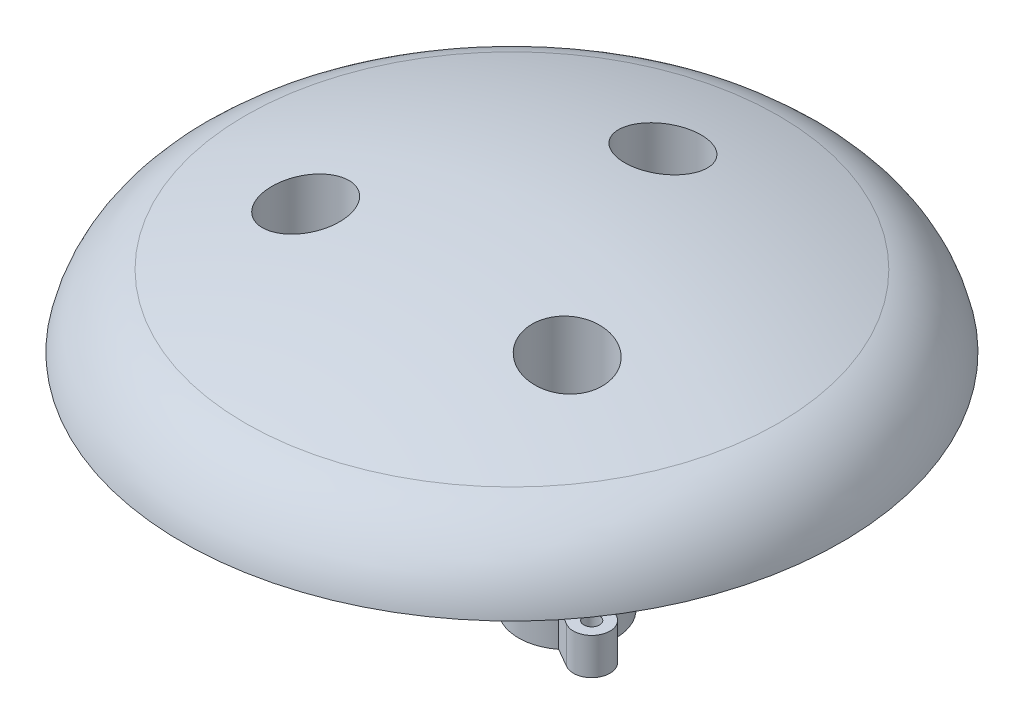
SolidWorks part; units mm, degrees
ref_plane "Alzado" through (0, 0, 0) normal (0, 0, 1) x (1, 0, 0)
ref_plane "Planta" through (0, 0, 0) normal (0, 1, 0) x (1, 0, 0)
ref_plane "Vista lateral" through (0, 0, 0) normal (1, 0, 0) x (0, 0, -1)
sketch "Croquis1" plane through (0, 0, 0) normal (0, 1, 0) x (1, 0, 0)
  line L1 (0, 28.8675) -> (-25, -14.4338) construction
  line L2 (-25, -14.4338) -> (25, -14.4338) construction
  line L3 (25, -14.4338) -> (0, 28.8675) construction
  circle A0 centre (0, 0) radius 14.4338 construction
  circle A1 centre (0, 28.8675) radius 7.3
  circle A2 centre (-25, -14.4338) radius 7.3
  circle A3 centre (25, -14.4338) radius 7.3
  circle A4 centre (0, 28.8675) radius 9.3
  circle A5 centre (25, -14.4338) radius 9.3
  circle A6 centre (-25, -14.4338) radius 9.3
  dimension "D2" = 14.6
  dimension "D1" = 50
  dimension "D5" = 2
sketch "Croquis2" plane through (0, 0, 0) normal (0, 0, 1) x (1, 0, 0)
  line L0 (0, 0) -> (0, 100) construction
  line L3 (0, 100) -> (0, 97)
  line L6 (50.9554, 91.6692) -> (50, 88.8254) construction
  line L8 (50, 88.8254) -> (0, -60) construction
  line L9 (60.0701, 77.4034) -> (63.0112, 77.995)
  line L11 (60.0701, 77.4034) -> (45.1548, 74.4036) construction
  arc A2 (0, 100) -> (50.9554, 91.6692) centre (0, -60) cw
  arc A3 (0, 97) -> (50, 88.8254) centre (0, -60) cw
  arc A4 (50.9554, 91.6692) -> (63.0112, 77.995) centre (45.1548, 74.4036) cw
  arc A5 (50, 88.8254) -> (60.0701, 77.4034) centre (45.1548, 74.4036) cw
  arc A6 (50, 88.8254) -> (60.0701, 77.4034) centre (45.1548, 74.4036) cw construction
  dimension "D1" = 100
  dimension "D4" = 50
  dimension "D3" = 160
  dimension "D2" = 3
  dimension "D5" = 3
revolve "Revolución1" add sketch "Croquis2" angle 360 about L0 other way angle 360
sketch "Croquis5" plane through (0, 0, 0) normal (0, 1, 0) x (1, 0, 0)
  circle A0 centre (0, 0) radius 50
  dimension "D1" = 100
extrude "Saliente-Extruir2" add sketch "Croquis5" along normal up to surface (3.8254 mm away) from offset 85 up to face at (0, 88.8254, -50)
extrude "Saliente-Extruir1" add sketch "Croquis1" along normal blind 37 from offset 55
sketch "Croquis3" plane through (0, 0, 0) normal (0, 1, 0) x (1, 0, 0)
  line L1 (0, 28.8675) -> (-25, -14.4338) construction
  line L2 (-25, -14.4338) -> (25, -14.4338) construction
  line L3 (25, -14.4338) -> (0, 28.8675) construction
  circle A0 centre (0, 0) radius 14.4338 construction
  circle A1 centre (0, 28.8675) radius 7.3
  circle A2 centre (-25, -14.4338) radius 7.3
  circle A3 centre (25, -14.4338) radius 7.3
  circle A4 centre (0, 28.8675) radius 9.3
  circle A5 centre (25, -14.4338) radius 9.3
  circle A6 centre (-25, -14.4338) radius 9.3
  dimension "D2" = 14.6
  dimension "D1" = 50
  dimension "D5" = 2
extrude "Cortar-Extruir1" cut sketch "Croquis3" along normal through all contours A3 | A1 | A2 region at (0, 0, -28.8675) region at (-25, 0, 14.4338) region at (25, 0, 14.4338)
sketch "Croquis12" plane through (0, 55, 0) normal (0, -1, 0) x (1, 0, 0)
  line L0 (34.3351, -23.8648) -> (-37.8351, 17.8027)
  line L1 (34.3351, -23.8648) -> (37.8351, -17.8027)
  line L2 (-37.8351, 17.8027) -> (-34.3351, 23.8648)
  line L3 (37.8351, -17.8027) -> (-34.3351, 23.8648)
  line L4 (34.3351, -23.8648) -> (-34.3351, 23.8648) construction
  line L5 (-37.8351, 17.8027) -> (37.8351, -17.8027) construction
  line L6 (-36.0851, 20.8338) -> (36.0851, -20.8338) construction
  line L7 (0, 0) -> (37.3119, 23.7338) construction
  line L8 (0, 0) -> (0, -36.1675) construction
  line L9 (-33.2388, 15.149) -> (-29.7388, 21.2111)
  circle A0 centre (-36.0851, 20.8338) radius 3.5
  circle A1 centre (-36.0851, 20.8338) radius 1.5
  circle A2 centre (0, -28.8675) radius 7.3 construction
  circle A3 centre (0, -28.8675) radius 7.3 construction
  circle A4 centre (-25, 14.4338) radius 9.3 construction
  point P4 (0, 0)
  circle M9 centre (-25, 14.4338) radius 9.3
  dimension "D2" = 3
  dimension "D3" = 7
  dimension "D1" = 60
extrude "Saliente-Extruir6" add sketch "Croquis12" against normal blind 7 contours L0 L9 L3 M9 | A0 L0 M9 | A0 L3 M9 | A1 L2 A0 | A1 L2 A0 region at (-32.1855, 55, 18.5823) region at (-34.8839, 55, 17.0245) region at (-37.537, 55, 21.672) region at (-34.6333, 55, 19.9955) region at (-32.1856, 55, 21.6981)
sketch "Croquis10" plane through (0, 0, 0) normal (0, 0, 1) x (1, 0, 0)
  line L0 (0, 47) -> (0, 70) construction
  line L1 (-5, 47) -> (-5, 70)
  line L2 (5, 47) -> (5, 70)
  line L3 (0, 85) -> (0, 55) construction
  line L4 (-9.3, 55) -> (9.3, 55) construction
  line L5 (-9.3, 85) -> (9.3, 85) construction
  arc A0 (-5, 47) -> (5, 47) centre (0, 47) ccw
  arc A1 (5, 70) -> (-5, 70) centre (0, 70) ccw
  point P3 (0, 58.5)
  dimension "D3" = 5
  dimension "D1" = 8
  dimension "D2" = 15
extrude "Cortar-Extruir4" cut sketch "Croquis10" against normal blind 25
pattern_circular "MatrizC1" count 3 over 360 about axis through (0, 77.4034, 0) along (0, -1, 0) of "Cortar-Extruir4", "Saliente-Extruir6"
fillet "Redondeo2" radius 5 3 edges at (0, 85, -19.5675) (25, 85, 23.7338) (-25, 85, 23.7338)
fillet "Redondeo3" radius 7 1 edges at (0, 85, 50)
